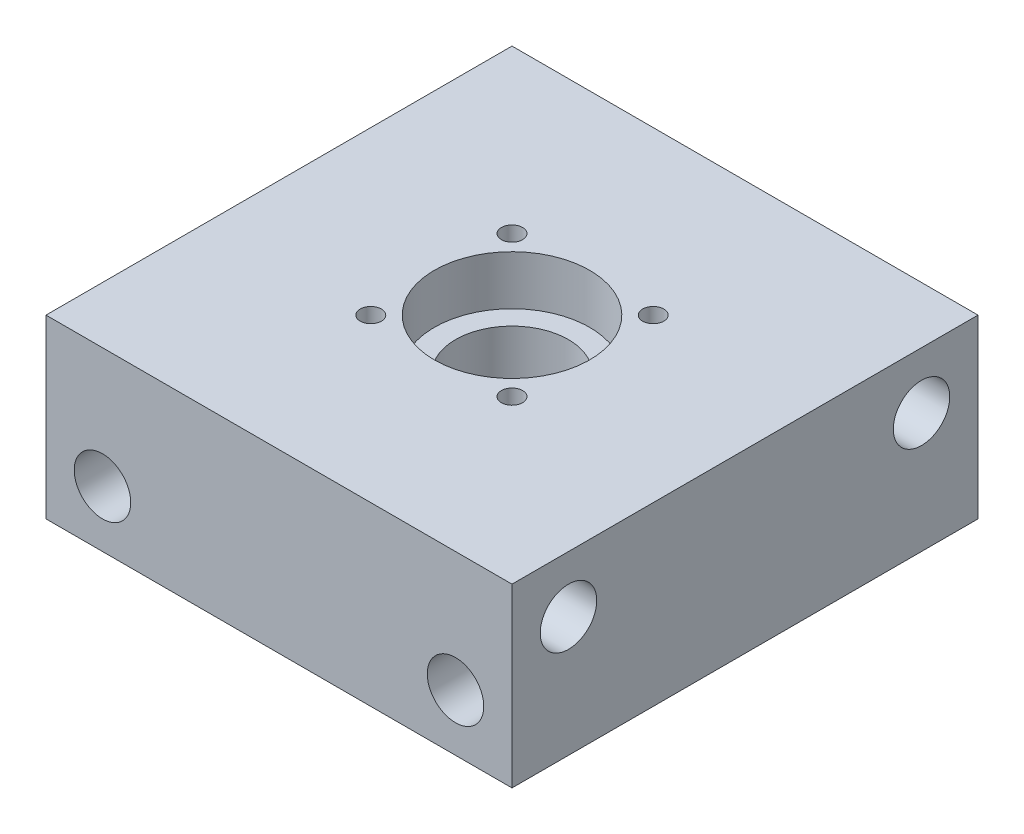
SolidWorks part; units mm, degrees
material "ABS"
ref_plane "Front Plane" through (0, 0, 0) normal (0, 0, 1) x (1, 0, 0)
ref_plane "Top Plane" through (0, 0, 0) normal (0, 1, 0) x (1, 0, 0)
ref_plane "Right Plane" through (0, 0, 0) normal (1, 0, 0) x (0, 0, -1)
sketch "Sketch1" plane through (0, 0, 0) normal (0, 1, 0) x (1, 0, 0)
  line L0 (-25, 94.322) -> (-25, -161.1056) construction
  line L1 (0, 212.1837) -> (0, -209.6879) construction
  line L2 (-178.557, 25) -> (189.3494, 25) construction
  line L3 (-284.8586, 0) -> (271.277, 0) construction
  line L4 (-33, 29) -> (33, 29)
  line L5 (-29, 33) -> (-21, 33)
  line L6 (-29, 33) -> (-29, -33)
  line L7 (-29, -33) -> (-21, -33)
  line L8 (-21, 33) -> (-21, -33)
  line L9 (-33, 21) -> (33, 21)
  line L10 (-33, -29) -> (-33, -21)
  line L11 (-178.557, -25) -> (189.3494, -25) construction
  line L12 (33, -29) -> (33, -21)
  line L13 (-33, 29) -> (33, 29)
  line L14 (-33, 29) -> (-33, 21)
  line L15 (-33, 21) -> (33, 21)
  line L16 (33, 29) -> (33, 21)
  line L17 (-33, -21) -> (33, -21)
  line L18 (-33, -29) -> (33, -29)
  line L19 (-33, -21) -> (33, -21)
  line L20 (-33, -29) -> (33, -29)
  line L21 (29, -33) -> (21, -33)
  line L22 (29, 33) -> (21, 33)
  line L23 (25, 94.322) -> (25, -161.1056) construction
  line L24 (21, 33) -> (21, -33)
  line L25 (29, 33) -> (29, -33)
  line L26 (13.2332, 10) -> (11.6166, 12.8)
  line L27 (-33, 33) -> (33, 33)
  line L28 (-33, 33) -> (-33, -33)
  line L29 (-33, -33) -> (33, -33)
  line L30 (33, 33) -> (33, -33)
  line L31 (-6.7668, 10) -> (-8.3834, 12.8)
  line L32 (-8.3834, 12.8) -> (-11.6166, 12.8)
  line L33 (-11.6166, 12.8) -> (-13.2332, 10)
  line L34 (-13.2332, 10) -> (-11.6166, 7.2)
  line L35 (-11.6166, 7.2) -> (-8.3834, 7.2)
  line L36 (-8.3834, 7.2) -> (-6.7668, 10)
  line L37 (11.6166, 12.8) -> (8.3834, 12.8)
  line L38 (8.3834, 12.8) -> (6.7668, 10)
  line L39 (6.7668, 10) -> (8.3834, 7.2)
  line L40 (8.3834, 7.2) -> (11.6166, 7.2)
  line L41 (11.6166, 7.2) -> (13.2332, 10)
  line L42 (13.2332, -10) -> (11.6166, -7.2)
  line L43 (11.6166, -7.2) -> (8.3834, -7.2)
  line L44 (8.3834, -7.2) -> (6.7668, -10)
  line L45 (6.7668, -10) -> (8.3834, -12.8)
  line L46 (8.3834, -12.8) -> (11.6166, -12.8)
  line L47 (11.6166, -12.8) -> (13.2332, -10)
  line L48 (-6.7668, -10) -> (-8.3834, -7.2)
  line L49 (-8.3834, -7.2) -> (-11.6166, -7.2)
  line L50 (-11.6166, -7.2) -> (-13.2332, -10)
  line L51 (-13.2332, -10) -> (-11.6166, -12.8)
  line L52 (-11.6166, -12.8) -> (-8.3834, -12.8)
  line L53 (-8.3834, -12.8) -> (-6.7668, -10)
  circle A0 centre (0, 0) radius 11
  circle A1 centre (0, 0) radius 8
  circle A2 centre (-10, 10) radius 1.5
  circle A3 centre (10, 10) radius 1.5
  circle A4 centre (10, 10) radius 2.8 construction
  circle A5 centre (10, -10) radius 1.5
  circle A6 centre (-10, 10) radius 2.8 construction
  circle A7 centre (10, -10) radius 2.8 construction
  circle A8 centre (-10, -10) radius 1.5
  circle A9 centre (-10, -10) radius 2.8 construction
  dimension "D5" = 2
  dimension "D6" = 2
  dimension "D7" = 3
  dimension "D14" = 5.6
  dimension "D2" = 25
  dimension "D3" = 25
  dimension "D4" = 4
  dimension "D8" = 10
  dimension "D9" = 10
  dimension "D12" = 8
  dimension "D13" = 4
extrude "Boss-Extrude1" add sketch "Sketch1" along normal blind 25 contours L24 L9 L8 L17 A3 A2 A0 | L24 L4 L8 L9 | L6 L9 L8 L4 | L27 L8 L4 L24 | L8 L5 L6 L4 | L27 L28 L4 L6 | L4 L14 L9 L6 | L9 L28 L17 L6 | L6 L17 L8 L9 | L6 L18 L8 L17 | L10 L18 L6 L17 | L28 L29 L6 L18 | L18 L6 L7 L8 | L24 L17 L8 L18 | L8 L29 L24 L18 | L25 L20 L24 L21 | L25 L19 L24 L20 | L17 L25 L18 L12 | L30 L18 L25 L29 | L25 L15 L24 L19 | L30 L9 L25 L17 | L25 L13 L24 L15 | L4 L25 L9 L16 | L25 L22 L24 L13 | L30 L27 L25 L4 | L35 L36 L31 L32 L33 L34 A2 | L40 L41 L26 L37 L38 L39 A3 | L46 L47 L42 L43 L44 L45 A5 | L52 L53 L48 L49 L50 L51 A8 region at (-31, 0, -31) region at (-31, 0, -25) region at (-25, 0, -31) region at (-25, 0, -25) region at (-31, 0, 0) region at (0, 0, -31) region at (0, 0, -25) region at (-25, 0, 0) region at (-31, 0, 25) region at (25, 0, -31) region at (25, 0, -25) region at (0, 0, -20.406) region at (-25, 0, 25) region at (-31, 0, 31) region at (31, 0, -31) region at (31, 0, -25) region at (25, 0, 0) region at (0, 0, 25) region at (-25, 0, 31) region at (31, 0, 0) region at (25, 0, 25) region at (0, 0, 31) region at (31, 0, 25) region at (25, 0, 31) region at (31, 0, 31) region at (12.3508, 0, -8.6428) region at (-7.6492, 0, -8.6428) region at (12.3508, 0, 11.3572) region at (-7.6492, 0, 11.3572)
extrude "Boss-Extrude2" add sketch "Sketch1<4>" along normal blind 18 contours A0 A1 region at (-10.6889, 0, 0)
sketch "Sketch1<4>" plane through (0, 0, 0) normal (0, 1, 0) x (1, 0, 0) same geometry as "Sketch1"
sketch "Sketch2" plane through (-33, 0, 0) normal (-1, 0, 0) x (0, 0, 1)
  line L0 (0, 0) -> (0, 25) construction
  line L1 (-33, 25) -> (33, 25) construction
  circle A0 centre (-25, 17) radius 4
  circle A1 centre (25, 17) radius 4
  dimension "D3" = 8
  dimension "D1" = 25
  dimension "D2" = 8
extrude "Cut-Extrude1" cut sketch "Sketch2" against normal through all
sketch "Sketch3" plane through (0, 0, -33) normal (0, 0, -1) x (-1, 0, 0)
  line L0 (0, 0) -> (0, 25) construction
  line L1 (33, 25) -> (-33, 25) construction
  line L2 (33, 0) -> (-33, 0) construction
  circle A0 centre (-25, 8) radius 4
  circle A1 centre (25, 8) radius 4
  dimension "D1" = 8
  dimension "D2" = 25
  dimension "D3" = 8
extrude "Cut-Extrude2" cut sketch "Sketch3" against normal through all
extrude "Cut-Extrude3" cut sketch "Sketch1<5>" along normal blind 2.5 contours L52 L53 L48 L49 L50 L51 A8 | L35 L36 L31 L32 L33 L34 A2 | L40 L41 L26 L37 L38 L39 A3 | L46 L47 L42 L43 L44 L45 A5 region at (12.3508, 0, -8.6428) region at (-7.6492, 0, -8.6428) region at (12.3508, 0, 11.3572) region at (-7.6492, 0, 11.3572)
sketch "Sketch1<5>" plane through (0, 0, 0) normal (0, 1, 0) x (1, 0, 0) same geometry as "Sketch1"
equation "\"rod_diameter\"= 8"
equation "\"rod_hole_thickness\"= 4"
equation "\"rod_radius\"= \"rod_diameter\" / 2"
equation "\"platter_diameter\"= 320"
equation "\"platter_radius\"= \"platter_diameter\" / 2"
equation "\"extruder_mount_hole_spacing\"= 75"
equation "\"arm_rod_spacing\"= 40"
equation "\"top_frame_rod_spacing\"= \"arm_rod_spacing\" + 40"
equation "\"motor_level_rod_spacing\"= 15"
equation "\"linear_bearing_diameter\"= 15"
equation "\"z_rod_spacing\"= 75"
equation "\"platter_rod_spacing\"= 50"
equation "\"rod_nut_thickness\"= 6.5"
equation "\"rod_nut_inscribed_diameter\"= 13"
equation "\"D2@Sketch1\"=\"platter_rod_spacing\"/2"
equation "\"D3@Sketch1\"=\"platter_rod_spacing\"/2"
equation "\"D12@Sketch1\"=\"rod_diameter\""
equation "\"D4@Sketch1\"=\"rod_hole_thickness\""
equation "\"D13@Sketch1\"=\"rod_hole_thickness\""
equation "\"D1@Boss-Extrude1\"= \"rod_diameter\" * 2 + \"rod_hole_thickness\" * 2 + 1"
equation "\"D1@Boss-Extrude2\"= \"D1@Boss-Extrude1\" - 7"
equation "\"D1@Sketch2\"=\"platter_rod_spacing\"/2"
equation "\"D2@Sketch2\"=\"rod_radius\"+\"rod_hole_thickness\""
equation "\"D3@Sketch2\"=\"rod_diameter\""
equation "\"D1@Sketch3\"=\"rod_diameter\""
equation "\"D2@Sketch3\"=\"platter_rod_spacing\"/2"
equation "\"D3@Sketch3\"=\"rod_radius\"+\"rod_hole_thickness\""
